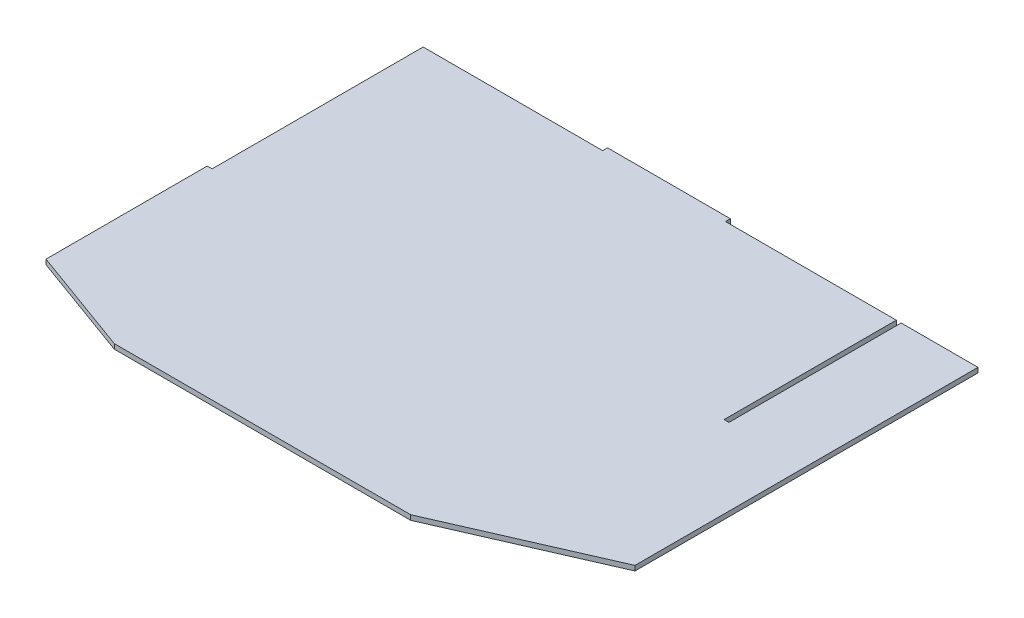
SolidWorks part; units mm, degrees
material "6061-T6 (SS)"
ref_plane "X-Y Datum" through (0, 0, 0) normal (0, 0, 1) x (1, 0, 0)
ref_plane "X-Z Datum" through (0, 0, 0) normal (0, 1, 0) x (1, 0, 0)
ref_plane "Y-Z Datum" through (0, 0, 0) normal (1, 0, 0) x (0, 0, -1)
sketch "Sketch1" plane through (0, 0, 0) normal (0, 0, 1) x (1, 0, 0)
  line L1 (-155.6385, -1.5875) -> (155.6385, -1.5875)
  line L2 (-155.6385, -1.5875) -> (-155.6385, 1.5875)
  line L3 (-155.6385, 1.5875) -> (155.6385, 1.5875)
  line L4 (155.6385, -1.5875) -> (155.6385, 1.5875)
  line L5 (-155.6385, -1.5875) -> (155.6385, 1.5875) construction
  line L6 (-155.6385, 1.5875) -> (155.6385, -1.5875) construction
  point P0 (0, 0)
  dimension "D1" = 3.175
  dimension "D2" = 311.277
extrude "Boss-Extrude1" add sketch "Sketch1" along normal blind 267.83
sketch "Sketch3" plane through (155.6385, 0, 0) normal (1, 0, 0) x (0, 0, -1)
  line L0 (-267.83, 1.5875) -> (0, 1.5875) construction
  line L1 (-267.83, -1.5875) -> (-112.128, -1.5875)
  line L2 (-267.83, -1.5875) -> (-267.83, 1.5875)
  line L3 (-267.83, 1.5875) -> (-112.128, 1.5875)
  line L4 (-112.128, -1.5875) -> (-112.128, 1.5875)
  dimension "D1" = 155.702
extrude "Boss-Extrude3" add sketch "Sketch3" along normal blind 3.175
sketch "Sketch4" plane through (0, 0, 267.83) normal (0, 0, 1) x (1, 0, 0)
  line L1 (158.8135, -1.5875) -> (208.8515, -1.5875)
  line L2 (158.8135, -1.5875) -> (158.8135, 1.5875)
  line L3 (158.8135, 1.5875) -> (208.8515, 1.5875)
  line L4 (208.8515, -1.5875) -> (208.8515, 1.5875)
  dimension "D1" = 3.175
  dimension "D2" = 50.038
extrude "Boss-Extrude4" add sketch "Sketch4" against normal blind 267.83
sketch "Sketch6" plane through (0, 1.5875, 0) normal (0, 1, 0) x (1, 0, 0)
  line L0 (107.2515, -267.83) -> (107.2515, -223.38)
  line L1 (208.8515, -267.83) -> (-155.6385, -267.83) construction
  line L2 (208.8515, -223.38) -> (107.2515, -223.38)
  line L3 (208.8515, 0) -> (208.8515, -267.83) construction
  line L4 (107.2515, -267.83) -> (208.8515, -223.38)
  line M9 (-155.6385, -267.83) -> (208.8515, -267.83)
  line M10 (208.8515, -267.83) -> (208.8515, 0)
  dimension "D1" = 44.45
  dimension "D2" = 101.6
extrude "Cut-Extrude1" cut sketch "Sketch6" against normal through all contours L4 M9 M10 region at (174.9848, 1.5875, 253.0133)
sketch "Sketch8" plane through (0, 0, 0) normal (0, 0, -1) x (-1, 0, 0)
  line L1 (35.5815, 1.5875) -> (-44.4185, 1.5875)
  line L2 (35.5815, 1.5875) -> (35.5815, -1.5875)
  line L3 (35.5815, -1.5875) -> (-44.4185, -1.5875)
  line L4 (-44.4185, 1.5875) -> (-44.4185, -1.5875)
extrude "Boss-Extrude6" add sketch "Sketch8" along normal blind 3.175
sketch "Sketch10" plane through (0, -1.5875, 0) normal (0, -1, 0) x (1, 0, 0)
  line L1 (-155.6385, 0) -> (-152.4635, 0)
  line L2 (-155.6385, 0) -> (-155.6385, 137.414)
  line L3 (-155.6385, 137.414) -> (-152.4635, 137.414)
  line L4 (-152.4635, 0) -> (-152.4635, 137.414)
  dimension "D1" = 137.414
  dimension "D2" = 3.175
extrude "Cut-Extrude2" cut sketch "Sketch10" against normal through all
sketch "Sketch11" plane through (0, -1.5875, 0) normal (0, -1, 0) x (1, 0, 0)
  line L0 (-85.7885, 267.83) -> (-85.7885, 242.43)
  line L1 (-155.6385, 267.83) -> (107.2515, 267.83) construction
  line L2 (-155.6385, 242.43) -> (-85.7885, 242.43)
  line L3 (-155.6385, 267.83) -> (-155.6385, 137.414) construction
  line L4 (-155.6385, 242.43) -> (-85.7885, 267.83)
  line M4 (-155.6385, 267.83) -> (-155.6385, 137.414)
  line M18 (107.2515, 267.83) -> (-155.6385, 267.83)
  dimension "D1" = 69.85
  dimension "D2" = 25.4
extrude "Cut-Extrude3" cut sketch "Sketch11" against normal through all contours L4 M4 M18 region at (-132.3552, -1.5875, 259.3633)
